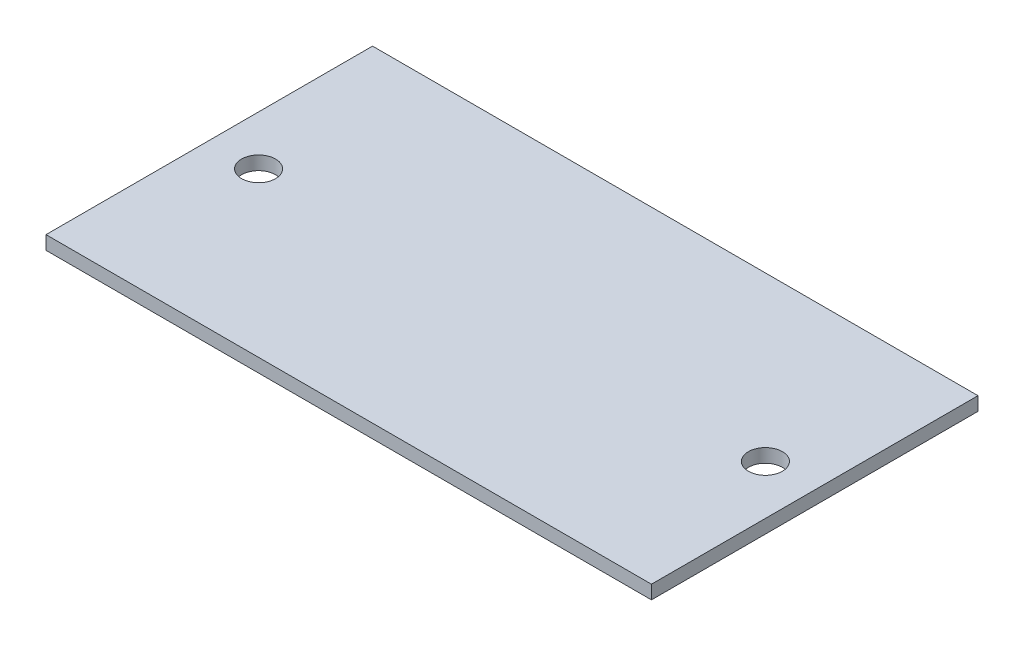
SolidWorks part; units mm, degrees
ref_plane "Front Plane" through (0, 0, 0) normal (0, 0, 1) x (1, 0, 0)
ref_plane "Top Plane" through (0, 0, 0) normal (0, 1, 0) x (1, 0, 0)
ref_plane "Right Plane" through (0, 0, 0) normal (1, 0, 0) x (0, 0, -1)
sketch "Sketch1" plane through (0, 0, 0) normal (0, 1, 0) x (1, 0, 0)
  line L0 (0, -12) -> (0, 12) construction
  line L1 (-22.25, -12) -> (22.25, -12)
  line L2 (-22.25, -12) -> (-22.25, 12)
  line L3 (-22.25, 12) -> (22.25, 12)
  line L4 (22.25, -12) -> (22.25, 12)
  line L5 (-22.25, -12) -> (22.25, 12) construction
  line L6 (-22.25, 12) -> (22.25, -12) construction
  line L7 (15, -12) -> (15, 12) construction
  line L8 (15, -12) -> (22.25, 12) construction
  circle A0 centre (18.625, 0) radius 1.25
  circle A1 centre (-18.625, 0) radius 1.25
  point P0 (0, 0)
  point P9 (0, 0)
  point P12 (15, 0)
  dimension "D4" = 2.5
  dimension "D1" = 44.5
  dimension "D2" = 24
  dimension "D3" = 7.25
extrude "Boss-Extrude1" add sketch "Sketch1" along normal blind 1
